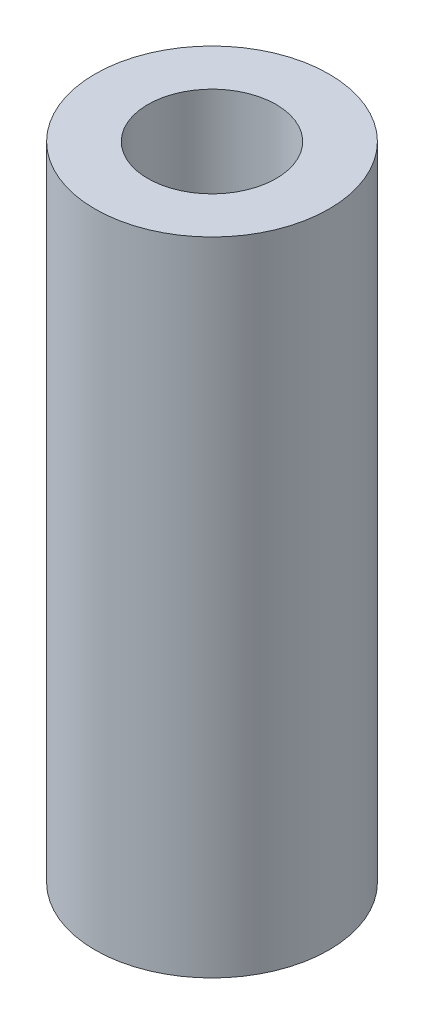
SolidWorks part; units mm, degrees
material "Natural Rubber"
ref_plane "Front Plane" through (0, 0, 0) normal (0, 0, 1) x (1, 0, 0)
ref_plane "Top Plane" through (0, 0, 0) normal (0, 1, 0) x (1, 0, 0)
ref_plane "Right Plane" through (0, 0, 0) normal (1, 0, 0) x (0, 0, -1)
sketch "Sketch2" plane through (0, 0, 0) normal (0, 1, 0) x (1, 0, 0)
  circle A0 centre (0, 0) radius 55.5625
  circle A1 centre (0, 0) radius 30.48
extrude "Boss-Extrude1" add sketch "Sketch2" along normal blind 304.8
